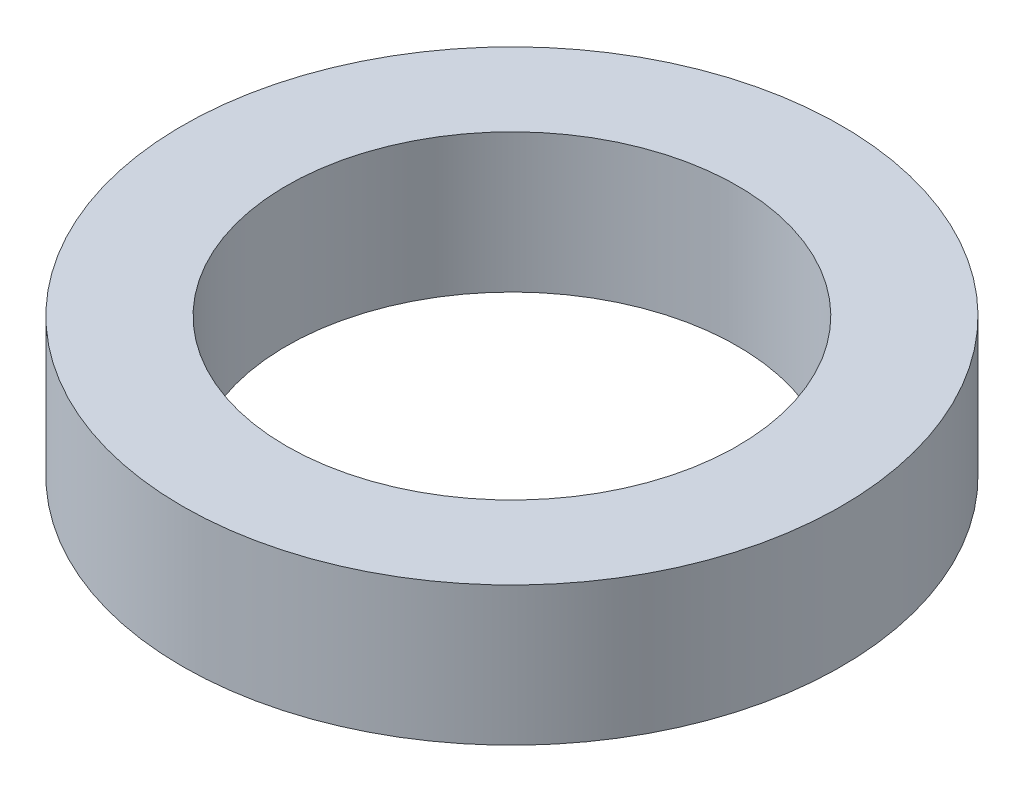
SolidWorks part; units mm, degrees
ref_plane "Front Plane" through (0, 0, 0) normal (0, 0, 1) x (1, 0, 0)
ref_plane "Top Plane" through (0, 0, 0) normal (0, 1, 0) x (1, 0, 0)
ref_plane "Right Plane" through (0, 0, 0) normal (1, 0, 0) x (0, 0, -1)
sketch "Sketch1" plane through (0, 0, 0) normal (0, 1, 0) x (1, 0, 0)
  circle A0 centre (0, 0) radius 47.5
  dimension "FLANGE_OD" = 95
extrude "Boss-Extrude1" add sketch "Sketch1" along normal blind 20
sketch "Sketch2" plane through (0, 0, 0) normal (0, 1, 0) x (1, 0, 0)
  circle A0 centre (0, 0) radius 32.5
  dimension "BORE_D" = 65
extrude "Cut-Extrude1" cut sketch "Sketch2" along normal through all
sketch "Sketch3" plane through (0, 20, 0) normal (0, 1, 0) x (1, 0, 0)
  circle A0 centre (0, 0) radius 18.1221 construction
  circle A1 centre (-18.1221, 0) radius 2.3377
  dimension "BOLT_D" = 4.6755
  dimension "BOLT_PCD" = 36.2441
extrude "Cut-Extrude2" cut sketch "Sketch3" against normal blind 12.1938 rebuild error yes
pattern_circular "CirPattern1" count 5 over 360 rebuild error yes
